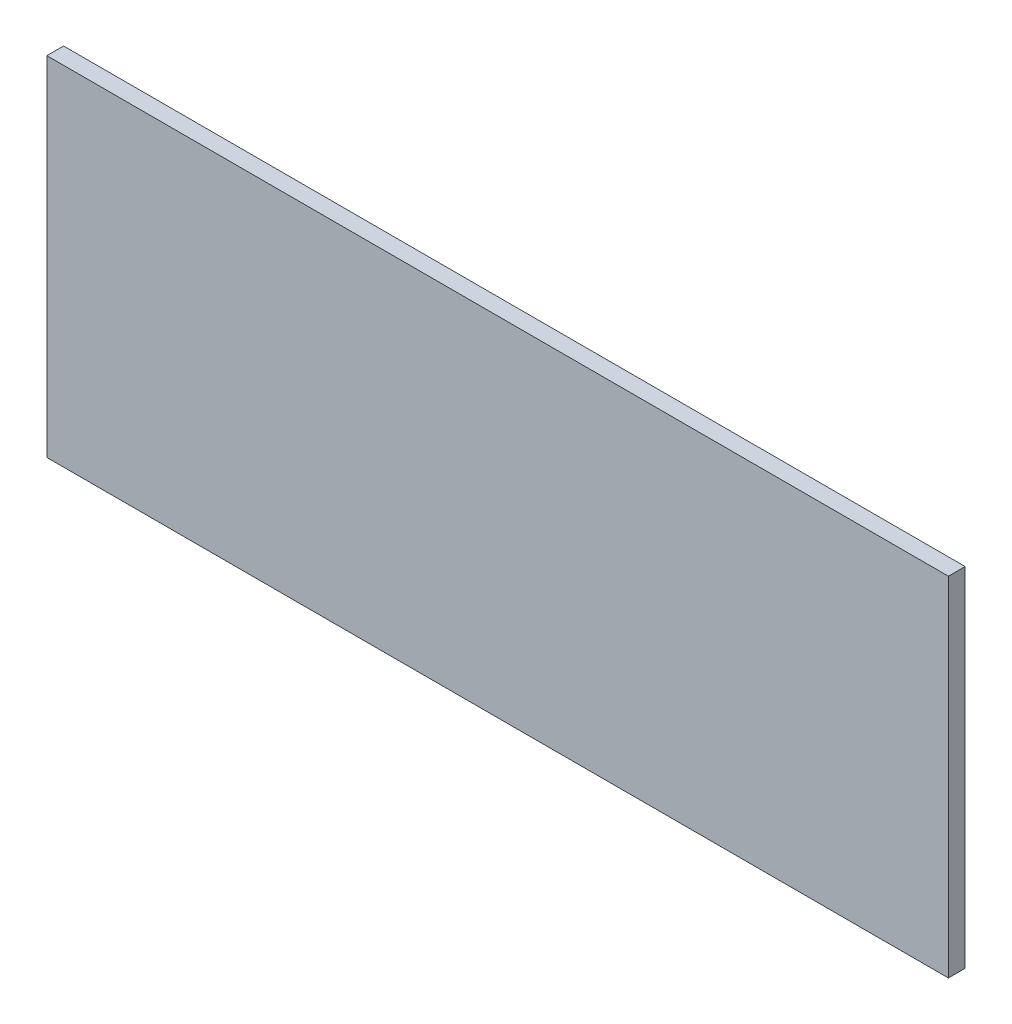
SolidWorks part; units mm, degrees
ref_plane "Front Plane" through (0, 0, 0) normal (0, 0, 1) x (1, 0, 0)
ref_plane "Top Plane" through (0, 0, 0) normal (0, 1, 0) x (1, 0, 0)
ref_plane "Right Plane" through (0, 0, 0) normal (1, 0, 0) x (0, 0, -1)
sketch "Sketch1" plane through (0, 0, 0) normal (0, 0, 1) x (1, 0, 0)
  line L1 (0, 0) -> (342, 0)
  line L2 (0, 0) -> (0, 132)
  line L3 (0, 132) -> (342, 132)
  line L4 (342, 0) -> (342, 132)
  dimension "D1" = 132
  dimension "D2" = 342
extrude "Boss-Extrude1" add sketch "Sketch1" along normal blind 6.35
